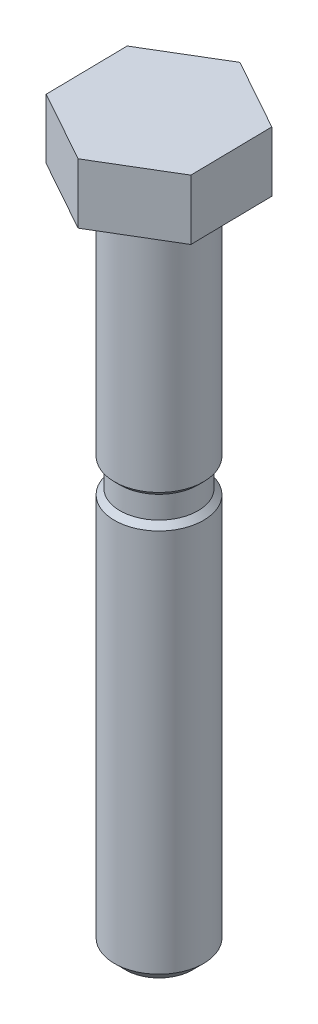
SolidWorks part; units mm, degrees
ref_plane "Front Plane" through (0, 0, 0) normal (0, 0, 1) x (1, 0, 0)
ref_plane "Top Plane" through (0, 0, 0) normal (0, 1, 0) x (1, 0, 0)
ref_plane "Right Plane" through (0, 0, 0) normal (1, 0, 0) x (0, 0, -1)
sketch "Sketch1" plane through (0, 0, 0) normal (0, 1, 0) x (1, 0, 0)
  line L1 (6.4576, -3.5934) -> (6.3408, 3.7958)
  line L2 (6.3408, 3.7958) -> (-0.1169, 7.3892)
  line L3 (-0.1169, 7.3892) -> (-6.4576, 3.5934)
  line L4 (-6.4576, 3.5934) -> (-6.3408, -3.7958)
  line L5 (-6.3408, -3.7958) -> (0.1169, -7.3892)
  line L6 (0.1169, -7.3892) -> (6.4576, -3.5934)
  circle A0 centre (0, 0) radius 6.4 construction
  dimension "D1" = 12.8
extrude "Boss-Extrude1" add sketch "Sketch1" along normal blind 5.4
sketch "Sketch3" plane through (0, 0, 0) normal (0, -1, 0) x (1, 0, 0)
  circle A0 centre (0, 0) radius 4
extrude "Boss-Extrude2" add sketch "Sketch3" along normal blind 60
ref_plane "Plane1" through (0, -23, 0) normal (0, -1, 0) x (-1, 0, 0)
sketch "Sketch4" plane through (0, -23, 0) normal (0, -1, 0) x (-1, 0, 0)
  circle A0 centre (0, 0) radius 3.5032
  circle A1 centre (0, 0) radius 4.3995
extrude "Cut-Extrude1" cut sketch "Sketch4" against normal mid plane 2
chamfer "Chamfer1" distance 0.5 angle 45 2 edges at (0, -22, -4) (0, -24, -4)
chamfer "Chamfer2" distance 1 angle 45 1 edges at (0, -60, -4)
